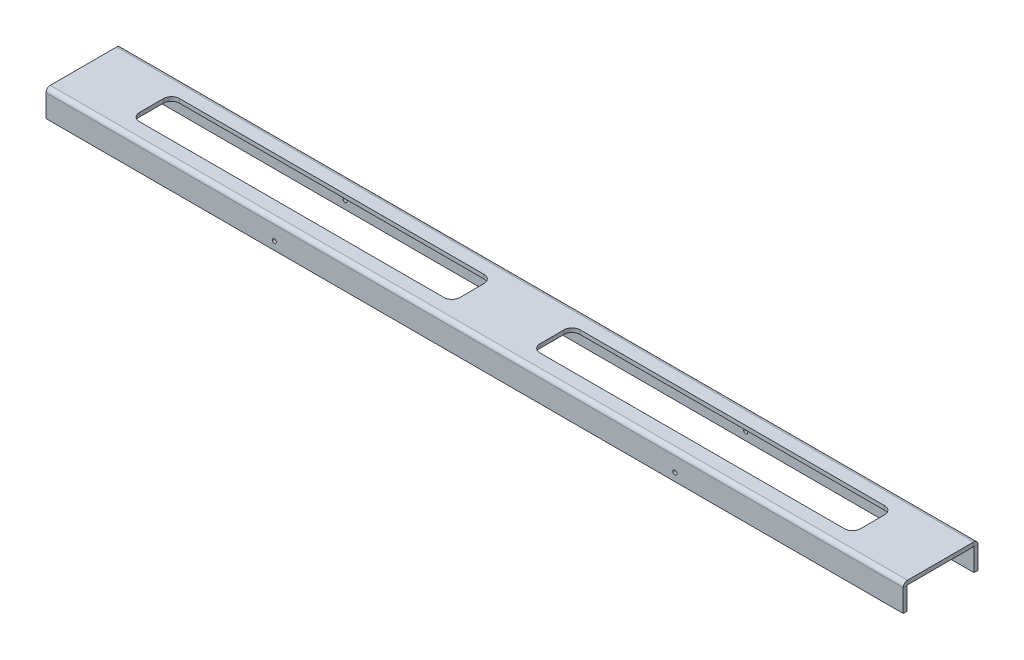
SolidWorks part; units mm, degrees
note: The reader was unsure of these and kept them because the rebuilt part matched: thickness of "基体-法兰1", "边线-法兰1", "边线-法兰2", "钣金6", "钣金7", "钣金8", "钣金14", "钣金15", "钣金16", "钣金17"; flange length of "边线-法兰1", "边线-法兰2".
material "冷轧钢板"
ref_plane "前视基准面" through (0, 0, 0) normal (0, 0, 1) x (1, 0, 0)
ref_plane "上视基准面" through (0, 0, 0) normal (0, 1, 0) x (1, 0, 0)
ref_plane "右视基准面" through (0, 0, 0) normal (1, 0, 0) x (0, 0, -1)
sketch "草图1" plane through (0, 0, 0) normal (0, 0, 1) x (1, 0, 0)
  line L1 (-160.5, 30) -> (160.5, 30)
  line L2 (-160.5, 30) -> (-160.5, -30)
  line L3 (-160.5, -30) -> (160.5, -30)
  line L4 (160.5, 30) -> (160.5, -30)
  line L5 (-160.5, 30) -> (160.5, -30) construction
  line L6 (-160.5, -30) -> (160.5, 30) construction
  point P0 (0, 0)
  dimension "D1" = 321
  dimension "D2" = 60
base flange "基体-法兰1" sketch "草图1" thickness 1.5 reverse thickness direction no parameters "D1"=0.1
edge flange "边线-法兰1" sketch "草图10" flange profiles "草图10", "草图11" flange angle 90 flange length 28 flange position material inside bend radius 0.1 thickness 1.5 parameters "D1"=0.5, "D6"=10, "D8"=1
sketch "草图10" plane through (0, 30, 0) normal (0, 1, 0) x (-1, 0, 0)
  line L2 (-160.5, 0) -> (-160.5, 26.5)
  line L3 (-160.5, 26.5) -> (160.5, 26.5)
  line L4 (160.5, 26.5) -> (160.5, 0)
  line L5 (-160.5, 0) -> (160.5, 0) construction
  line L6 (-160.5, 0) -> (160.5, 0)
sketch "草图11" plane through (0, -30, 0) normal (0, -1, 0) x (1, 0, 0)
  line L0 (-160.5, 0) -> (160.5, 0) construction
  line L1 (-160.5, 0) -> (160.5, 0)
  line L2 (-160.5, 0) -> (-160.5, 26.5)
  line L3 (-160.5, 26.5) -> (160.5, 26.5)
  line L4 (160.5, 26.5) -> (160.5, 0)
bend "边线折弯1" bend radius 0.1 bend angle 90 parameters "D5"=1
bend "边线折弯2" bend radius 0.1 bend angle 90 parameters "D5"=2
edge flange "边线-法兰2" sketch "草图16" flange profiles "草图16", "草图17" flange angle 90 flange length 10 flange position material inside bend radius 0.1 thickness 1.5 parameters "D1"=0.5, "D6"=10, "D8"=1
sketch "草图16" plane through (0, 28.5, 26.5) normal (0, 0, -1) x (1, 0, 0)
  line L1 (160.5, 0) -> (-160.5, 0) construction
  line L2 (-160.5, 0) -> (-160.5, 8.5)
  line L3 (-160.5, 8.5) -> (160.5, 8.5)
  line L4 (160.5, 8.5) -> (160.5, 0)
  line L5 (160.5, 0) -> (-160.5, 0)
sketch "草图17" plane through (0, -28.5, 26.5) normal (0, 0, -1) x (-1, 0, 0)
  line L0 (160.5, 0) -> (-160.5, 0) construction
  line L1 (160.5, 0) -> (-160.5, 0)
  line L2 (160.5, 0) -> (160.5, 8.5)
  line L3 (160.5, 8.5) -> (-160.5, 8.5)
  line L4 (-160.5, 8.5) -> (-160.5, 0)
bend "边线折弯3" bend radius 0.1 bend angle 90 parameters "D5"=3
bend "边线折弯4" bend radius 0.1 bend angle 90 parameters "D5"=4
sketch "草图19" plane through (0, 30, 0) normal (0, 1, 0) x (1, 0, 0)
  line L0 (0, 36.0868) -> (0, -45.539) construction
  line L1 (-160.5, 1.5) -> (160.5, 1.5) construction
  line L2 (-132, -5) -> (-18, -5)
  line L3 (-135, -8) -> (-135, -17)
  line L4 (-132, -20) -> (-18, -20)
  line L5 (-15, -8) -> (-15, -17)
  line L6 (-135, -5) -> (-15, -20) construction
  line L7 (-135, -20) -> (-15, -5) construction
  arc A0 (-18, -5) -> (-15, -8) centre (-18, -8) cw
  arc A1 (-15, -17) -> (-18, -20) centre (-18, -17) cw
  arc A2 (-132, -20) -> (-135, -17) centre (-132, -17) cw
  arc A3 (-135, -8) -> (-132, -5) centre (-132, -8) cw
  point P3 (-75, -12.5)
  dimension "D5" = 3
  dimension "D1" = 120
  dimension "D2" = 15
  dimension "D3" = 14
  dimension "D4" = 75
extrude "切除-拉伸2" cut sketch "草图19" against normal through all normal cut yes
mirror "镜向1" about plane through (0, 0, 0) normal (1, 0, 0) of "切除-拉伸2"
sketch "草图20" plane through (0, 0, 0) normal (0, 0, 1) x (1, 0, 0)
  line L1 (-180.5875, -54.9106) -> (160.5, -54.9106)
  line L2 (-180.5875, -54.9106) -> (-180.5875, 20)
  line L3 (-180.5875, 20) -> (160.5, 20)
  line L4 (160.5, -54.9106) -> (160.5, 20)
extrude "切除-拉伸3" cut sketch "草图20" along normal blind 57 and the other way blind 10 normal cut yes
sketch "草图21" plane through (0, 0, 26.5) normal (0, 0, 1) x (1, 0, 0)
  line L0 (0, 20) -> (0, 30) construction
  line L1 (-160.5, 20) -> (160.5, 20) construction
  line L2 (-160.5, 30) -> (160.5, 30) construction
  line L3 (-75, 23) -> (75, 23) construction
  line L4 (160.5, 20) -> (-160.5, 20) construction
  circle A0 centre (75, 23) radius 0.75
  circle A1 centre (-75, 23) radius 0.75
  point P10 (0, 23)
  dimension "D1" = 1.5
  dimension "150" = 150
  dimension "D2" = 3
extrude "切除-拉伸4" cut sketch "草图21" against normal through all both and the other way through all normal cut yes
sketch "折弯-线1" [suppressed] plane through (0, 0, 0) normal (0, 1, 0) x (-1, 0, 0)
sketch "边界框1" [suppressed] plane through (0, 0, 0) normal (0, 1, 0) x (-1, 0, 0)
sheet metal parameters "钣金6" thickness 1.5 parameters "D1"=0.1, "D7"=1
flat pattern "平板型式6" [suppressed]
sketch "折弯-线2" plane through (0, 0, 0) normal (0, 1, 0) x (-1, 0, 0)
sketch "边界框2" [suppressed] plane through (0, 0, 0) normal (0, 1, 0) x (-1, 0, 0)
sheet metal parameters "钣金7" thickness 1.5 parameters "D1"=0.1, "D7"=1
flat pattern "平板型式6" [suppressed]
sketch "折弯-线2" plane through (0, 0, 0) normal (0, 1, 0) x (-1, 0, 0)
sketch "边界框2" [suppressed] plane through (0, 0, 0) normal (0, 1, 0) x (-1, 0, 0)
bend of the flat pattern "展开-<边线折弯1>1"
bend of the flat pattern "展开-<边线折弯2>1"
sheet metal parameters "钣金8" thickness 1.5 parameters "D1"=0.1, "D7"=1
flat pattern "平板型式6" [suppressed]
sketch "折弯-线2" plane through (0, 0, 0) normal (0, 1, 0) x (-1, 0, 0)
sketch "边界框2" [suppressed] plane through (0, 0, 0) normal (0, 1, 0) x (-1, 0, 0)
bend of the flat pattern "展开-<边线折弯1>1"
bend of the flat pattern "展开-<边线折弯2>1"
bend of the flat pattern "展开-<边线折弯3>1"
bend of the flat pattern "展开-<边线折弯4>1"
sheet metal parameters "钣金14" thickness 1.5 parameters "D1"=0.1, "D7"=1
flat pattern "平板型式6"
sketch "折弯-线2" plane through (0, 0, 0) normal (0, 0, 1) x (1, 0, 0)
  line L0 (-168, -55.45) -> (168, -55.45) construction
  line L1 (168, 55.45) -> (-168, 55.45) construction
  line L2 (-168, -29.15) -> (168, -29.15) construction
  line L3 (168, 29.15) -> (-168, 29.15) construction
  line L4 (-168, -55.45) -> (168, -55.45) construction
  line L5 (168, 55.45) -> (-168, 55.45) construction
  line L6 (-168, -29.15) -> (168, -29.15) construction
  line L7 (168, 29.15) -> (-168, 29.15) construction
sketch3d "边界框2" [suppressed]
  line L0 (-168, -64.6, 0) -> (168, -64.6, 0) construction
  line L1 (-168, 64.6, 0) -> (168, 64.6, 0) construction
  line L2 (-168, -64.6, 0) -> (-168, 64.6, 0) construction
  line L3 (168, -64.6, 0) -> (168, 64.6, 0) construction
bend of the flat pattern "展开-<边线折弯1>1"
bend of the flat pattern "展开-<边线折弯2>1"
bend of the flat pattern "展开-<边线折弯3>1"
bend of the flat pattern "展开-<边线折弯4>1"
sheet metal parameters "钣金15" thickness 1.5 parameters "D1"=0.1, "D7"=1
flat pattern "平板型式6"
sketch "折弯-线2" plane through (0, 0, 0) normal (0, 0, 1) x (1, 0, 0)
  line L0 (-168, -55.45) -> (168, -55.45) construction
  line L1 (168, 55.45) -> (-168, 55.45) construction
  line L2 (-168, -29.15) -> (168, -29.15) construction
  line L3 (168, 29.15) -> (-168, 29.15) construction
  line L4 (-168, -55.45) -> (168, -55.45) construction
  line L5 (168, 55.45) -> (-168, 55.45) construction
  line L6 (-168, -29.15) -> (168, -29.15) construction
  line L7 (168, 29.15) -> (-168, 29.15) construction
sketch3d "边界框2" [suppressed]
  line L0 (-168, -64.6, 0) -> (168, -64.6, 0) construction
  line L1 (-168, 64.6, 0) -> (168, 64.6, 0) construction
  line L2 (-168, -64.6, 0) -> (-168, 64.6, 0) construction
  line L3 (168, -64.6, 0) -> (168, 64.6, 0) construction
bend of the flat pattern "展开-<边线折弯1>1"
bend of the flat pattern "展开-<边线折弯2>1"
bend of the flat pattern "展开-<边线折弯3>1"
bend of the flat pattern "展开-<边线折弯4>1"
sheet metal parameters "钣金16" thickness 1.5 parameters "D1"=0.1, "D7"=1
flat pattern "平板型式6"
sketch "折弯-线2" plane through (0, 0, 0) normal (0, 0, 1) x (1, 0, 0)
  line L1 (160.5, 55.45) -> (-160.5, 55.45) construction
  line L3 (160.5, 29.15) -> (-160.5, 29.15) construction
  line L5 (160.5, 55.45) -> (-160.5, 55.45) construction
  line L7 (160.5, 29.15) -> (-160.5, 29.15) construction
sketch3d "边界框2" [suppressed]
  line L0 (-160.5, 20, 0) -> (160.5, 20, 0) construction
  line L1 (-160.5, 64.6, 0) -> (160.5, 64.6, 0) construction
  line L2 (-160.5, 20, 0) -> (-160.5, 64.6, 0) construction
  line L3 (160.5, 20, 0) -> (160.5, 64.6, 0) construction
bend of the flat pattern "展开-<边线折弯3>1"
bend of the flat pattern "展开-<边线折弯1>1"
sheet metal parameters "钣金17" thickness 1.5 parameters "D1"=0.1, "D7"=1
flat pattern "平板型式6"
sketch "折弯-线2" plane through (0, 0, 0) normal (0, 0, 1) x (1, 0, 0)
  line L1 (160.5, 54.25) -> (-160.5, 54.25) construction
  line L3 (160.5, 28.75) -> (-160.5, 28.75) construction
  line L5 (160.5, 54.25) -> (-160.5, 54.25) construction
  line L7 (160.5, 28.75) -> (-160.5, 28.75) construction
sketch3d "边界框2" [suppressed]
  line L0 (-160.5, 20, 0) -> (160.5, 20, 0) construction
  line L1 (-160.5, 63, 0) -> (160.5, 63, 0) construction
  line L2 (-160.5, 20, 0) -> (-160.5, 63, 0) construction
  line L3 (160.5, 20, 0) -> (160.5, 63, 0) construction
bend of the flat pattern "展开-<边线折弯3>1"
bend of the flat pattern "展开-<边线折弯1>1"
